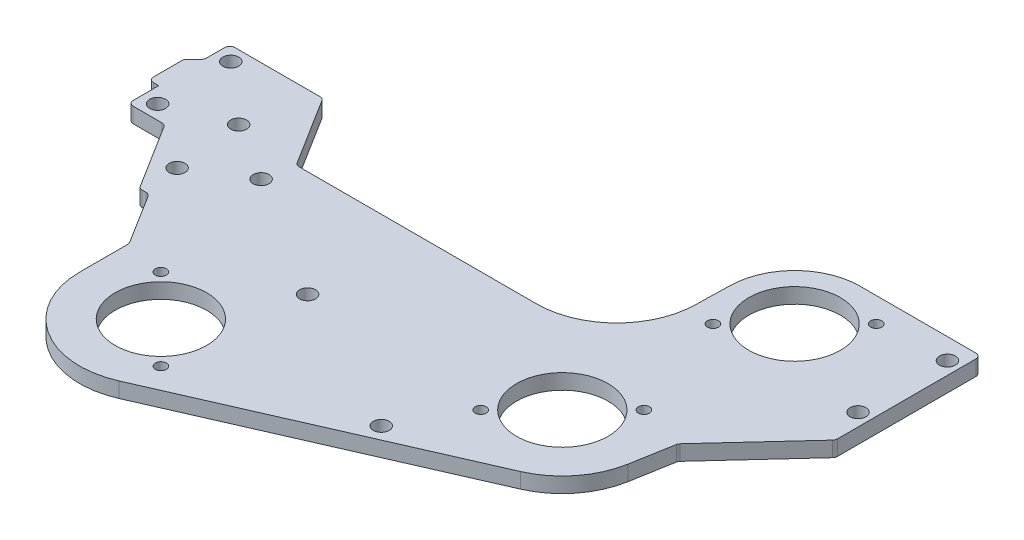
SolidWorks part; units mm, degrees
material "6061 Alloy"
ref_plane "Front Plane" through (0, 0, 0) normal (0, 0, 1) x (1, 0, 0)
ref_plane "Top Plane" through (0, 0, 0) normal (0, 1, 0) x (1, 0, 0)
ref_plane "Right Plane" through (0, 0, 0) normal (1, 0, 0) x (0, 0, -1)
sketch "Sketch1" plane through (0, 0, 0) normal (0, 1, 0) x (1, 0, 0)
  line L1 (-62.0382, -79.8833) -> (25.1671, -41.6958)
  line L5 (39.9402, -22.8907) -> (42.2751, -9.5867)
  line L6 (42.2751, -9.5867) -> (65.831, 16.0128)
  line L16 (-92.7762, 6.1643) -> (-17.7344, 6.1643)
  line L19 (65.831, 61.4936) -> (28.0466, 61.4936)
  line L20 (65.831, 16.0128) -> (65.831, 61.4936)
  line L24 (-218.6325, 207.5765) -> (-97.2237, 13.2819) construction
  line L25 (-106.6713, 28.4011) -> (-92.7762, 6.1643)
  line L26 (-72.2583, -56.6285) -> (15.031, -18.5085) construction
  line L27 (-72.2269, -82.0164) -> (109.3231, -82.0164) construction
  line L28 (15.0167, -18.5164) -> (15.0167, -82.0164) construction
  line L29 (7.3775, 31.2763) -> (7.6, 41.2639)
  line L33 (-110.9585, -24.6526) -> (-138.654, 19.6694) construction
  line L34 (-110.9585, -24.6526) -> (-126.1313, -0.371) construction
  line L36 (-135.7546, 28.4011) -> (-106.6713, 28.4011)
  line L37 (-97.6599, -56.6285) -> (-97.6599, -41.1417)
  line L38 (-107.9634, -24.6526) -> (-97.6599, -41.1417)
  line L40 (-107.9634, -24.6526) -> (-110.9585, -24.6526)
  line L42 (-138.9296, 17.2827) -> (-138.9296, 6.1643)
  line L43 (-92.7762, 6.1643) -> (-138.9296, 6.1643) construction
  line L44 (-138.9296, 6.1643) -> (-135.7546, 6.1643)
  line L45 (-135.7546, 6.1643) -> (-135.7546, -3.3607)
  line L46 (-135.7546, -3.3607) -> (-124.2632, -3.3607)
  line L47 (-124.2632, -3.3607) -> (-110.9585, -24.6526)
  line L48 (-135.7546, 6.1643) -> (-135.7546, 28.4011) construction
  line L49 (-138.9296, 17.2827) -> (-135.7546, 20.4577)
  line L50 (-135.7546, 20.4577) -> (-135.7546, 28.4011)
  circle A0 centre (28.0466, 41.0458) radius 14.29
  circle A1 centre (15.031, -18.5085) radius 14.29
  circle A2 centre (-72.2583, -56.6285) radius 14.29
  arc A4 (39.9402, -22.8907) -> (25.1671, -41.6958) centre (15.0167, -18.5164) cw
  circle A7 centre (15.031, -18.5085) radius 25.4 construction
  circle A8 centre (-72.2583, -56.6285) radius 25.4 construction
  circle A9 centre (-28.6137, -37.5685) radius 22.225 construction
  circle A10 centre (28.0466, 41.0458) radius 30.48 construction
  circle A11 centre (15.031, -18.5085) radius 30.48 construction
  arc A14 (-17.7344, 6.1643) -> (7.3775, 31.2763) centre (-17.7344, 31.2763) ccw
  arc A15 (7.6, 41.2639) -> (28.0466, 61.4936) centre (28.0466, 41.0458) cw
  arc A16 (-62.0382, -79.8833) -> (-97.6599, -56.6285) centre (-72.2583, -56.6285) cw
  point P11 (-62.0382, -79.8833)
  point P34 (15.0167, -18.5164)
  point P35 (28.0466, 41.0458)
  dimension "D2" = 50.8
  dimension "D3" = 50.8
  dimension "D4" = 44.45
  dimension "D5" = 63.5
  dimension "D7" = 60.96
  dimension "D8" = 60.96
  dimension "D1" = 140.0048
  dimension "D6" = 95.25
  dimension "D9" = 50.8
  dimension "D10" = 143.51
extrude "Boss-Extrude1" add sketch "Sketch1" along normal blind 4.7625
hole_wizard "#10 Clearance Hole1" positions "Sketch2" profile "Sketch3" hole size "#10" standard "ANSI Inch" end condition through all
sketch "Sketch2" plane through (0, 4.7625, 0) normal (0, 1, 0) x (1, 0, 0)
  point P0 (61.8305, 55.0158)
  point P3 (61.8305, 27.0758)
  point P7 (-130.9921, 23.9443)
  point P10 (-130.9921, 1.0843)
sketch "Sketch3" plane through (61.8305, 4.7625, -55.0158) normal (1, 0, 0) x (0, 0, 1)
  line L0 (0, 0) -> (0, 4.7625)
  line L1 (0, 4.7625) -> (2.4892, 4.7625)
  line L2 (2.4892, 4.7625) -> (2.4892, 0)
  line L5 (2.4892, 0) -> (0, 0)
  line L11 (0, -6.35) -> (0, 107.95) construction
  dimension "Thru Hole Dia." = 4.9784
  dimension "Thru Hole Depth" = 4.7625
sketch "Sketch4" plane through (0, 4.7625, 0) normal (0, 1, 0) x (1, 0, 0)
  line L0 (-72.2583, -56.6285) -> (-102.5432, -8.1625) construction
  line L1 (-102.5432, -8.1625) -> (-94.4656, -3.115) construction
  line L2 (-102.5432, -8.1625) -> (-110.6209, -13.21) construction
  line L3 (-102.5432, -8.1625) -> (-112.7324, 8.1436) construction
  line L4 (-102.5432, -8.1625) -> (-174.2713, 106.6264) construction
  line L5 (65.831, 41.0458) -> (65.831, 28.3458) construction
  dimension "D1" = 57.15
  dimension "D2" = 19.05
  dimension "D3" = 32
hole_wizard "#10 Clearance Hole2" positions "Sketch5" profile "Sketch6" hole size "#10" standard "ANSI Inch" end condition through all
sketch "Sketch5" plane through (0, 4.7625, 0) normal (0, 1, 0) x (1, 0, 0)
  point P0 (-110.6209, -13.21)
  point P3 (-94.4656, -3.115)
  point P7 (-112.7324, 8.1436)
sketch "Sketch6" plane through (-110.6209, 4.7625, 13.21) normal (1, 0, 0) x (0, 0, 1)
  line L0 (0, 0) -> (0, 4.7625)
  line L1 (0, 4.7625) -> (2.4892, 4.7625)
  line L2 (2.4892, 4.7625) -> (2.4892, 0)
  line L5 (2.4892, 0) -> (0, 0)
  line L11 (0, -6.35) -> (0, 107.95) construction
  dimension "Thru Hole Dia." = 4.9784
  dimension "Thru Hole Depth" = 4.7625
sketch "Sketch7" plane through (0, 4.7625, 0) normal (0, 1, 0) x (1, 0, 0)
  line L0 (-59.5064, -69.3804) -> (-85.0103, -43.8765) construction
  line L1 (2.279, -31.2604) -> (27.783, -5.7565) construction
  line L3 (15.2946, 28.2939) -> (40.7985, 53.7978) construction
  point P7 (-72.2583, -56.6285)
  point P11 (15.031, -18.5085)
  point P13 (28.0466, 41.0458)
hole_wizard "Tap Drill for #8-32 Tap1" positions "Sketch8" profile "Sketch9" hole size "#8-32" standard "ANSI Inch" end condition through all
sketch "Sketch8" plane through (0, 4.7625, 0) normal (0, 1, 0) x (1, 0, 0)
  point P0 (-85.0103, -43.8765)
  point P3 (-59.5064, -69.3804)
  point P6 (2.279, -31.2604)
  point P9 (27.783, -5.7565)
  point P12 (15.2946, 28.2939)
  point P15 (40.7985, 53.7978)
sketch "Sketch9" plane through (-85.0103, 4.7625, 43.8765) normal (1, 0, 0) x (0, 0, 1)
  line L0 (0, 0) -> (0, 4.7625)
  line L1 (0, 4.7625) -> (1.7272, 4.7625)
  line L2 (1.7272, 4.7625) -> (1.7272, 0)
  line L5 (1.7272, 0) -> (0, 0)
  line L11 (0, -6.35) -> (0, 107.95) construction
  dimension "Thru Hole Dia." = 3.4544
  dimension "Thru Hole Depth" = 4.7625
hole_wizard "#10 Clearance Hole3" positions "Sketch11" profile "Sketch12" hole size "#10" standard "ANSI Inch" end condition through all
sketch "Sketch11" plane through (0, 4.7625, 0) normal (0, 1, 0) x (1, 0, 0)
  point P0 (-56.0414, -27.0192)
  point P3 (-8.9513, -51.0906)
sketch "Sketch12" plane through (-56.0414, 4.7625, 27.0192) normal (1, 0, 0) x (0, 0, 1)
  line L0 (0, 0) -> (0, 4.7625)
  line L1 (0, 4.7625) -> (2.4892, 4.7625)
  line L2 (2.4892, 4.7625) -> (2.4892, 0)
  line L5 (2.4892, 0) -> (0, 0)
  line L11 (0, -6.35) -> (0, 107.95) construction
  dimension "Thru Hole Dia." = 4.9784
  dimension "Thru Hole Depth" = 4.7625
fillet "Fillet1" radius 1.5875 14 edges at (-135.7546, 2.3813, 3.3607) (-124.2632, 2.3813, 3.3607) (65.831, 2.3813, -61.4936) (65.831, 2.3813, -16.0128) (42.2751, 2.3813, 9.5867) (-97.6599, 2.3813, 41.1417) (-92.7762, 2.3813, -6.1643) (-106.6713, 2.3813, -28.4011) (-138.9296, 2.3813, -17.2827) (-107.9634, 2.3813, 24.6526) (-110.9585, 2.3813, 24.6526) (-135.7546, 2.3813, -28.4011) (-135.7546, 2.3813, -20.4577) (-138.9296, 2.3813, -6.1643)
